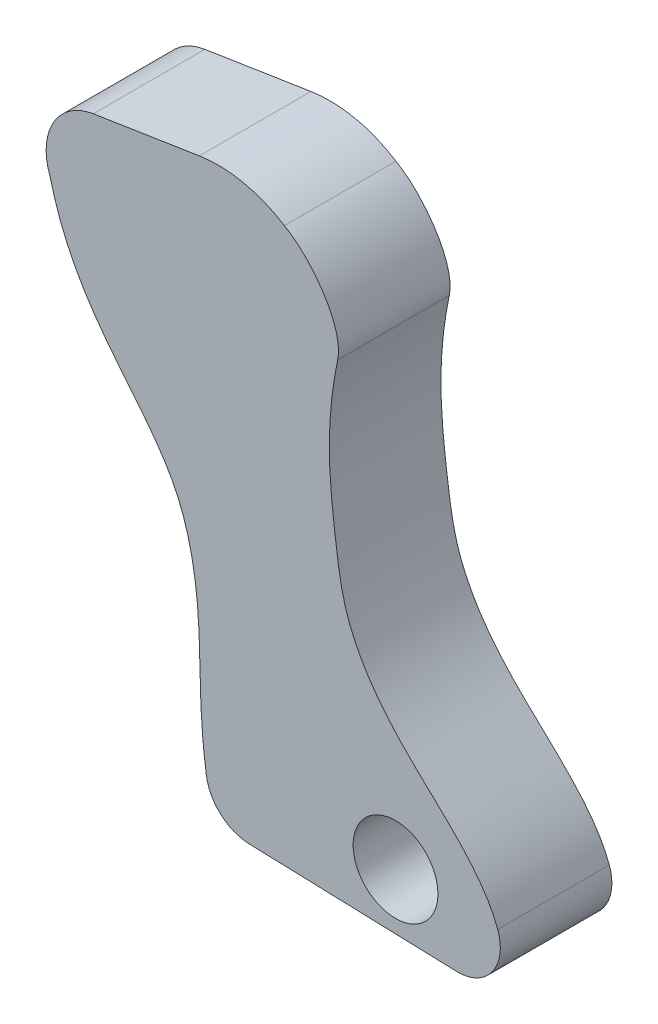
SolidWorks part; units mm, degrees
material "Chrome Stainless Steel"
ref_plane "Front Plane" through (0, 0, 0) normal (0, 0, 1) x (1, 0, 0)
ref_plane "Top Plane" through (0, 0, 0) normal (0, 1, 0) x (1, 0, 0)
ref_plane "Right Plane" through (0, 0, 0) normal (1, 0, 0) x (0, 0, -1)
sketch "Sketch1" plane through (0, 0, 0) normal (0, 0, 1) x (1, 0, 0)
  line L6 (-6.4682, 16.9638) -> (-2.1575, 4.0499) construction
  line L7 (-1.5237, -6.254) -> (3.2, -6.4072)
  line L8 (-5.0692, 6.3676) -> (-2.655, 6.7435)
  arc A8 (-2.4961, -5.3856) -> (-1.5237, -6.254) centre (-1.4908, -5.2385) ccw
  arc A9 (-6.0564, 4.6499) -> (-5.0692, 6.3676) centre (-4.8738, 5.1127) cw
  arc A10 (3.2, -6.4072) -> (4.1376, -5.1105) centre (3.2313, -5.4426) ccw
  arc A12 (-2.655, 6.7435) -> (-0.7183, 6.3356) centre (-2.2252, 3.9828) cw
  spline S0 degree 3 poles (4.1376, -5.1105) (3.7517, -4.0574) (1.9604, -2.8384) (0.6829, -0.8932) (0.4196, 0.8418) (0.2354, 2.4651) (0.3669, 3.682) (0.4939, 4.2967) knots 0 0 0 0 0.339615 0.543786 0.644515 0.831601 1 1 1 1
  spline S1 degree 3 poles (-6.0564, 4.6499) (-5.4726, 2.2476) (-3.1403, 0.9129) (-2.5644, -2.6474) (-2.6774, -4.1467) (-2.4961, -5.3856) knots 0 0 0 0 0.493395 0.716015 1 1 1 1
  spline S2 degree 3 poles (-0.7183, 6.3356) (-0.1212, 6.0072) (0.64, 5.0044) (0.4939, 4.2967) knots 0 0 0 0 1 1 1 1
  dimension "D1" = 1.27
  dimension "D2" = 2.794
  dimension "D3" = 1.016
  dimension "D4" = 0.9652
  dimension "D5" = 12.954
  dimension "D6" = 13.6144
  dimension "D7" = 3.7084
  dimension "D8" = 5.1816
  dimension "D9" = 1.9812
  dimension "D10" = 3.9878
  dimension "D11" = 4.4704
  dimension "D12" = 1.6002
  dimension "D13" = 3.6068
  dimension "D14" = 2.7432
  dimension ".089" = 2.2559
extrude "Boss-Extrude1" add sketch "Sketch1" along normal blind 2.54
hole_wizard "#48 (0.076) Diameter Hole1" positions "Sketch8" profile "Sketch4" hole size "#48" standard "ANSI Inch" end condition through all
sketch "Sketch8" plane through (0, 0, 2.54) normal (0, 0, 1) x (1, 0, 0)
  line L0 (-1.5237, -6.254) -> (3.2, -6.4072) construction
  arc A0 (-2.4961, -5.3856) -> (-1.5237, -6.254) centre (-1.4908, -5.2385) ccw construction
  point P0 (1.8112, -5.0915)
  dimension "D1" = 1.27
  dimension "D2" = 3.302
sketch "Sketch4" plane through (1.8112, -5.0915, 2.54) normal (1, 0, 0) x (0, -1, 0)
  line L0 (0, 0) -> (0, 2.54)
  line L1 (0, 2.54) -> (0.9652, 2.54)
  line L2 (0.9652, 2.54) -> (0.9652, 0)
  line L5 (0.9652, 0) -> (0, 0)
  line L11 (0, -6.35) -> (0, 107.95) construction
  dimension "Thru Hole Dia." = 1.9304
  dimension "Thru Hole Depth" = 2.54
